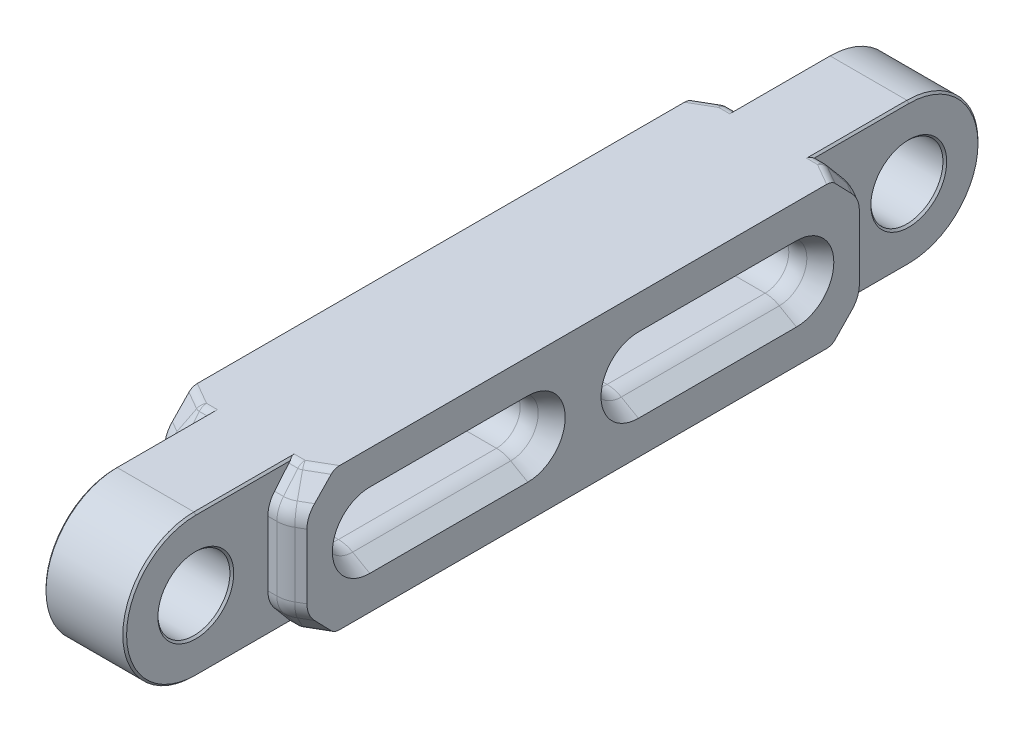
SolidWorks part; units mm, degrees
ref_plane "Front Plane" through (0, 0, 0) normal (1, 0, 0) x (0, 1, 0)
ref_plane "Top Plane" through (0, 0, 0) normal (0, 0, 1) x (0, 1, 0)
ref_plane "Right Plane" through (0, 0, 0) normal (0, 1, 0) x (-1, 0, 0)
sketch "Sketch1" plane through (0, 0, 0) normal (1, 0, 0) x (0, 1, 0)
  line L0 (-15, 0) -> (-15, -150.4)
  line L1 (-15, -75.2) -> (15, -75.2) construction
  line L2 (15, -150.4) -> (15, 0)
  line L3 (-5, -30.2) -> (-5, -63.5333)
  line L4 (-15, -135.2) -> (15, -135.2)
  line L6 (-15, -15.2) -> (15, -15.2)
  line L7 (0, 15) -> (0, -75.2)
  circle A0 centre (0, 0) radius 7.6
  circle A1 centre (0, 0) radius 15
  circle A26 centre (0, -150.4) radius 15
  circle A27 centre (0, -150.4) radius 7.6
  circle A28 centre (0, -63.5333) radius 5
  circle A29 centre (0, -30.2) radius 5
  point P16 (-5, -63.5333)
  point P17 (0, -68.5333)
  point P20 (0, -25.2)
  dimension "D1" = 30
  dimension "D2" = 15.2
  dimension "D3" = 15.2
  dimension "D4" = 120
  dimension "D5" = 10
  dimension "D6" = 6.6667
  dimension "D7" = 10
extrude "Boss-Extrude1" add sketch "Sketch1" along normal blind 8.5 contours L7 A1 A0 | A1 L0 L6 L7 | L0 L1 L7 L6 region at (0, -11.4068, -11.8513) region at (0, -10.3694, 10.3694) region at (0, -9.0049, -44.7055)
extrude "Boss-Extrude2" add sketch "Sketch1<4>" along normal blind 15 contours L0 L1 L7 L6 region at (0, -9.0049, -44.7055)
sketch "Sketch1<4>" plane through (0, 0, 0) normal (1, 0, 0) x (0, 1, 0) same geometry as "Sketch1"
chamfer "Chamfer8" distance 3 angle 30 1 edges at (15, -7.5, -15.2) first distance on face at (11.75, -7.5, -15.2)
fillet "Fillet6" radius 6 1 edges at (12, -7.5, -15.2)
chamfer "Chamfer9" distance 6 angle 40 3 edges at (14.1962, -15, -16.4679) (11.9452, -15, -15.4044) (9.4462, -15, -15.2) first distance on face at (14.1962, -7.5, -16.4679) first distance on face at (11.9188, -7.5, -15.5032) first distance on face at (9.4462, -7.5, -15.2)
fillet "Fillet7" radius 6 3 edges at (14.1962, -9, -16.4679) (11.9452, -9, -15.4044) (9.4462, -9, -15.2)
chamfer "Chamfer10" distance 5 angle 30 3 edges at (15, -3.5355, -67.0689) (15, -5, -46.8667) (15, -3.5355, -26.6645) first distance on face at (7.5, -3.0178, -66.5511) first distance on face at (7.5, -5, -46.8667) first distance on face at (7.5, -3.0178, -27.1822)
fillet "Fillet8" radius 6 3 edges at (10, -3.5355, -67.0689) (10, -5, -46.8667) (10, -3.5355, -26.6645)
fillet "Fillet9" radius 2 3 edges at (9.4462, -15, -20.2346) (10.6422, -15, -20.2675) (12.9375, -15, -21.5547)
chamfer "Chamfer11" distance 0.4 angle 45 3 edges at (8.5, -7.6, 0) (8.5, -15, -10.5836) (8.5, -10.6066, 10.6066)
mirror "Mirror1" about plane through (8.5, 0, 0) normal (0, 1, 0) of bodies 102
mirror "Mirror2" about plane through (8.5, 0, -75.2) normal (0, 0, 1) of bodies 108
mirror "Mirror3" about plane through (0, 0, 0) normal (1, 0, 0) of bodies 109
equation "\"D6@Sketch1\"=\"D5@Sketch1\"*2/3"
equation "\"D7@Sketch1\"=\"D5@Sketch1\""
